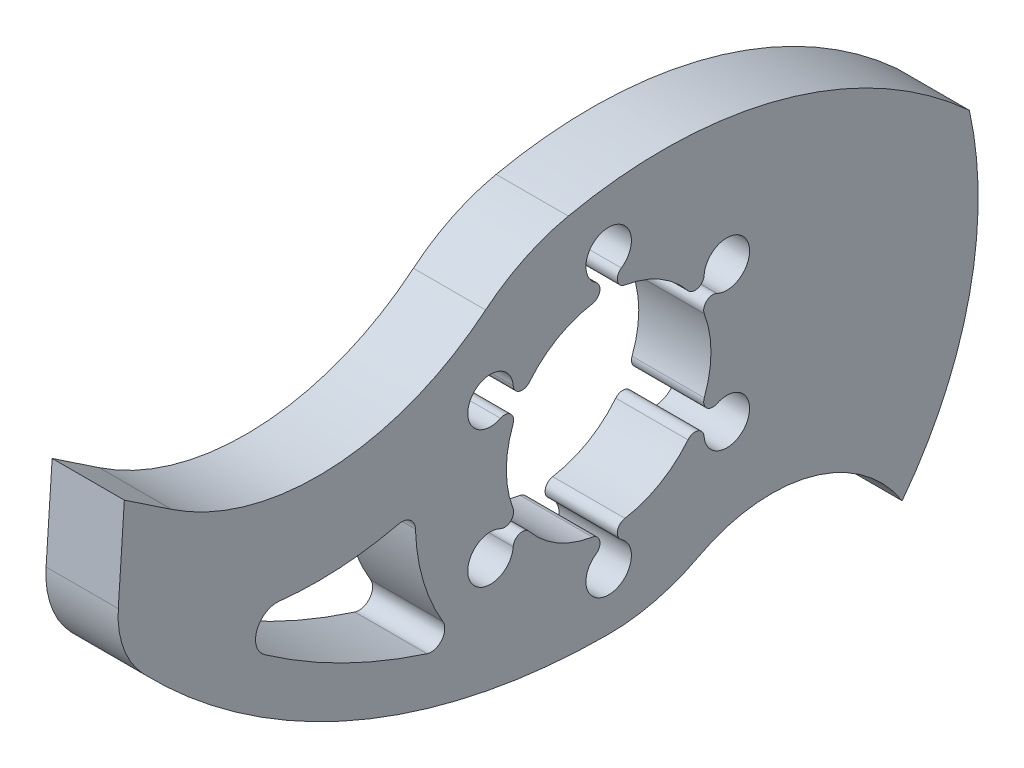
SolidWorks part; units mm, degrees
material "1023 Carbon Steel Sheet (SS)"
ref_plane "Front Plane" through (0, 0, 0) normal (0, 0, 1) x (1, 0, 0)
ref_plane "Top Plane" through (0, 0, 0) normal (0, 1, 0) x (1, 0, 0)
ref_plane "Right Plane" through (0, 0, 0) normal (1, 0, 0) x (0, 0, -1)
other "Center of Mass"
ref_plane "Plane1" through (6.35, 0, 0) normal (1, 0, 0) x (0, 0, -1)
sketch "Sketch1" plane through (0, 0, 0) normal (1, 0, 0) x (0, 0, -1)
  line L0 (-45, 0) -> (45, 0) construction
  line L1 (0, 12) -> (-10.3923, 6)
  line L2 (-10.3923, 6) -> (-10.3923, -6)
  line L3 (-10.3923, -6) -> (0, -12)
  line L4 (0, -12) -> (10.3923, -6)
  line L5 (10.3923, -6) -> (10.3923, 6)
  line L6 (10.3923, 6) -> (0, 12)
  line L7 (0, 45) -> (0, -45) construction
  circle A0 centre (0, 0) radius 45
  circle A1 centre (0, 0) radius 10.3923 construction
  circle A2 centre (0, 0) radius 17
  circle A3 centre (0, 0) radius 32.5
  circle A4 centre (0, 0) radius 9
  dimension "D1" = 90
  dimension "D3" = 34
  dimension "D4" = 65
  dimension "D5" = 18
  dimension "D2" = 24
sketch "Sketch2" plane through (0, 0, 0) normal (1, 0, 0) x (0, 0, -1)
  line L0 (-42.5954, 14.513) -> (-43.1289, 6.513)
  line L1 (-42.5954, 14.513) -> (0, 0) construction
  line L2 (-45, 0) -> (45, 0) construction
  line L3 (-42.5954, 14.513) -> (-38.4412, 11.7305)
  line L4 (31.7283, 7.0403) -> (21.8458, 16.0801) construction
  line L5 (25.8147, -19.7446) -> (20.7849, -11.8646) construction
  line L6 (-23.3781, -7.5057) -> (-25.1515, -11.0911) construction
  line L7 (-23.6822, -0.129) -> (-24.164, 7.8565) construction
  line L8 (31.7283, 7.0403) -> (25.8147, -19.7446) construction
  line L9 (0, 0) -> (28.7715, -6.3522) construction
  line L11 (-3.5483, 16.6256) -> (0, 0) construction
  circle A0 centre (0, 0) radius 45 construction
  arc A1 (-43.1289, 6.513) -> (-40.9039, 0.4262) centre (-35.1466, 5.9808) ccw
  arc A2 (-0.0524, -16.9999) -> (7.9477, -15.0278) centre (0, 0) ccw
  circle A3 centre (0, 0) radius 17 construction
  arc A4 (-10.8217, 13.1107) -> (-3.5483, 16.6256) centre (0, 0) cw
  arc A5 (-10.8217, 13.1107) -> (-38.4412, 11.7305) centre (-25.5582, 30.9642) cw
  arc A6 (-40.9039, 0.4262) -> (-0.0524, -16.9999) centre (0.1234, 40.0089) ccw
  arc A7 (7.9477, -15.0278) -> (25.8147, -19.7446) centre (14.3219, -27.0804) cw
  circle A8 centre (0, 0) radius 32.5 construction
  arc A9 (-3.5483, 16.6256) -> (31.7283, 7.0403) centre (4.7841, -22.4157) cw
  arc A10 (-16.9926, -0.5004) -> (-14.5838, -8.7358) centre (0, 0) ccw
  arc A11 (31.7283, 7.0403) -> (25.8147, -19.7446) centre (0, 0) cw
  arc A12 (-16.9926, -0.5004) -> (-18.4654, 0.6327) centre (-18.1921, -0.5357) ccw
  arc A13 (-14.5838, -8.7358) -> (-15.9777, -10.4957) centre (-15.6132, -9.3524) cw
  arc A14 (-15.9777, -10.4957) -> (-30.2457, -3.4385) centre (0.1234, 40.0089) cw
  arc A15 (-18.4654, 0.6327) -> (-28.9529, 0) centre (-25.5582, 30.9642) cw
  arc A16 (-28.9529, 0) -> (-30.2457, -3.4385) centre (-29.1595, -1.8846) ccw
  circle A17 centre (0, 0) radius 9
  circle A18 centre (0, 0) radius 9 construction
  dimension "D5" = 8
  dimension "D6" = 1.2
  dimension "D1" = 15
  dimension "D2" = 5
  dimension "D3" = 75
  dimension "D4" = 8
  dimension "D7" = 4
  dimension "D8" = 8
  dimension "D9" = 27.43
  dimension "D10" = 12.45
  dimension "D11" = 45
  dimension "D12" = 30
extrude "Boss-Extrude1" add sketch "Sketch2" along normal up to surface (6.35 mm away) up to plane "Plane1"
ref_axis "Axis1" through (0, 0, 0) along (1, 0, 0)
sketch "Sketch3" plane through (6.35, 0, 0) normal (1, 0, 0) x (0, 0, -1)
  circle A0 centre (0, 12) radius 2
  circle A1 centre (10.3923, 6) radius 2
  circle A2 centre (10.3923, -6) radius 2
  circle A3 centre (0, -12) radius 2
  circle A4 centre (-10.3923, -6) radius 2
  circle A5 centre (-10.3923, 6) radius 2
  dimension "D1" = 4
extrude "Cut-Extrude1" cut sketch "Sketch3" against normal through all
sketch "Sketch5" plane through (6.35, 0, 0) normal (1, 0, 0) x (0, 0, -1)
  line L0 (0, 12) -> (0, 0) construction
  arc A0 (-1.1145, 10.3393) -> (1.1145, 10.3393) centre (0, 12) ccw
  circle A1 centre (0, 12) radius 2 construction
  arc A2 (-1.1145, 10.3393) -> (-1.4329, 8.8852) centre (-1.5602, 9.675) cw
  arc A3 (-1.4329, 8.8852) -> (1.4329, 8.8852) centre (0, 0) cw
  circle A4 centre (0, 0) radius 9 construction
  arc A5 (1.1145, 10.3393) -> (1.4329, 8.8852) centre (1.5602, 9.675) ccw
  dimension "D1" = 0.8
extrude "Cut-Extrude2" cut sketch "Sketch5" against normal through all contours A3 A5 A0 A2
pattern_circular "CirPattern1" count 6 over 360 about axis through (0, 0, 0) along (1, 0, 0) of "Cut-Extrude2"
sketch "Sketch6" plane through (0, 0, 0) normal (1, 0, 0) x (0, 0, -1)
  circle A0 centre (0, 0) radius 29.2203 construction
  circle A1 centre (-29.1595, -1.8846) radius 1.8959 construction
sketch "Sketch4" plane through (0, 0, 0) normal (-1, 0, 0) x (0, 0, 1)
  circle A0 centre (0, 0) radius 17 construction
  circle A1 centre (0, 0) radius 17
  circle A2 centre (0, 0) radius 45 construction
  circle A3 centre (0, 0) radius 45
extrude "Boss-Extrude2" [suppressed] add sketch "Sketch4" against normal up to surface (6.35 mm away) up to face at (6.35, 0, 0)
